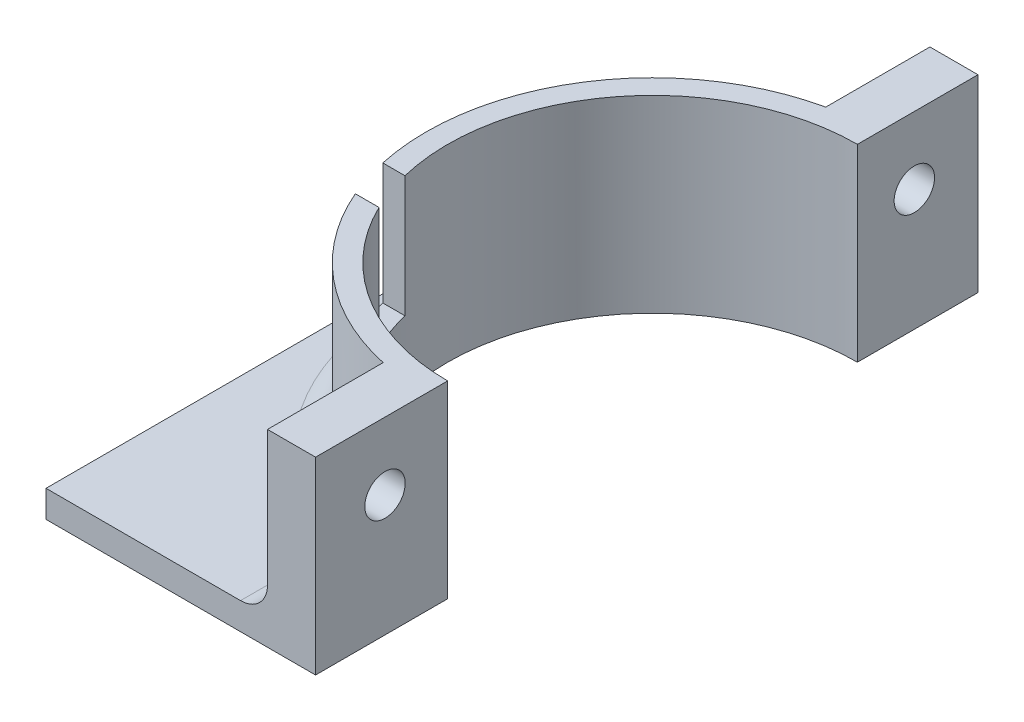
SolidWorks part; units mm, degrees
ref_plane "Front Plane" through (0, 0, 0) normal (0, 0, 1) x (1, 0, 0)
ref_plane "Top Plane" through (0, 0, 0) normal (0, 1, 0) x (1, 0, 0)
ref_plane "Right Plane" through (0, 0, 0) normal (1, 0, 0) x (0, 0, -1)
sketch "Sketch3" plane through (0, 0, 0) normal (0, 1, 0) x (1, 0, 0)
  line L0 (0, 0) -> (0, 62.4162)
  line L1 (0, 62.4162) -> (57.15, 62.4162)
  line L2 (57.15, 62.4162) -> (57.15, 0)
  line L3 (57.15, 0) -> (0, 0)
  line L4 (25.4, 62.4162) -> (25.4, 0)
  line L7 (20.8702, 62.4162) -> (20.8702, 52.5996)
  line L8 (29.9298, 62.4162) -> (29.9298, 52.5996)
  line L9 (20.8702, 0) -> (20.8702, 10.9004)
  line L10 (29.9298, 0) -> (29.9298, 10.9004)
  circle A0 centre (25.4, 31.75) radius 19.304
  arc A2 (20.8702, 52.5996) -> (20.8702, 10.9004) centre (25.4, 31.75) ccw
  arc A3 (29.9298, 10.9004) -> (29.9298, 52.5996) centre (25.4, 31.75) ccw
sketch "Sketch5" plane through (0, 0, 0) normal (1, 0, 0) x (0, 0, -1)
  circle A0 centre (6.5405, 11.43) radius 1.905
  circle A1 centre (56.4176, 11.43) radius 1.905
  point P2 (0, 0)
  point P3 (0, 0)
extrude "Boss-Extrude14" add sketch "Sketch3" along normal blind 2.54 contours A2 L7 L1 L0 L3 L9 region at (0.6581, 0, -31.2081)
extrude "Boss-Extrude15" add sketch "Sketch3<18>" along normal blind 17.78 contours L7 A2 L9 L3 L4 A0 L1 region at (21.5298, 0, -5.4502)
sketch "Sketch3<18>" plane through (0, 0, 0) normal (0, 1, 0) x (1, 0, 0) same geometry as "Sketch3"
fillet "Fillet3" radius 2.54 3 edges at (20.8702, 2.54, -57.5079) (4.064, 2.54, -31.75) (20.8702, 2.54, -5.4502)
extrude "Cut-Extrude3" cut sketch "Sketch5" along normal through all both and the other way through all
sketch "Sketch6" plane through (0, 0, 0) normal (1, 0, 0) x (0, 0, -1)
  line L3 (27.178, 6.35) -> (27.178, 17.78)
  line L4 (51.054, 17.78) -> (12.446, 17.78) construction
  line L5 (27.178, 17.78) -> (23.368, 17.78)
  line L6 (23.368, 17.78) -> (23.368, 6.35)
  line L7 (23.368, 6.35) -> (27.178, 6.35)
extrude "Cut-Extrude4" cut sketch "Sketch6" along normal through all both
